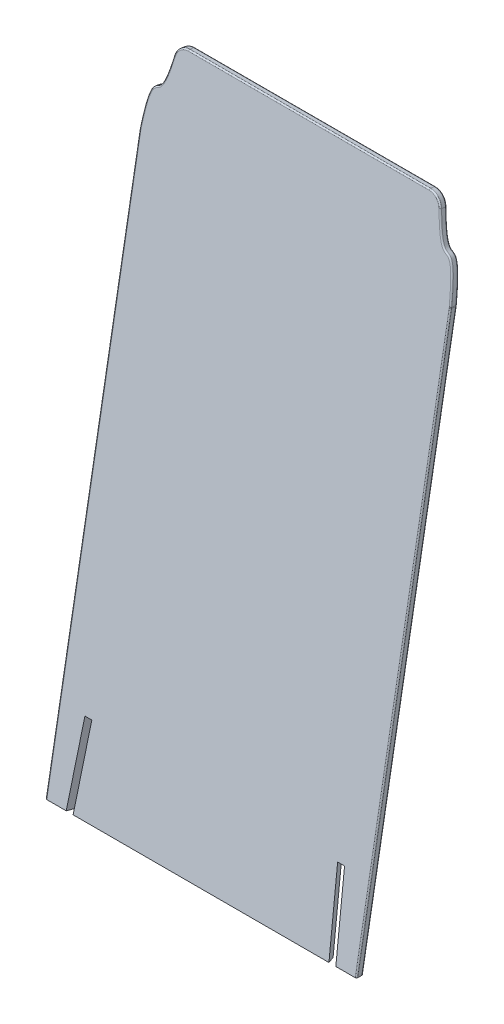
SolidWorks part; units mm, degrees
ref_plane "Front Plane" through (0, 0, 0) normal (0, 0, 1) x (1, 0, 0)
ref_plane "Top Plane" through (0, 0, 0) normal (0, 1, 0) x (1, 0, 0)
ref_plane "Right Plane" through (0, 0, 0) normal (1, 0, 0) x (0, 0, -1)
sketch "Sketch1" plane through (0, 0, 0) normal (1, 0, 0) x (0, 0, -1)
  line L0 (0, 0) -> (211.7119, 1200.6776)
  line L1 (211.7119, 1200.6776) -> (224.2189, 1198.4723)
  line L2 (224.2189, 1198.4723) -> (12.8959, 0)
  line L3 (55, 0) -> (-55, 0) construction
  line L4 (12.8959, 0) -> (0, 0)
  line L5 (0, 55) -> (0, -55) construction
  dimension "D1" = 12.7
  dimension "D2" = 10
  dimension "D3" = 1219.2
extrude "Boss-Extrude1" add sketch "Sketch1" along normal blind 609.6
ref_axis "Axis1" through (0, 1260.7115, 0) along (0, -1, 0)
ref_plane "Plane1" through (0, 0, 0) normal (-0.342, 0, 0.9397) x (0, -1, 0)
sketch "Sketch2" plane through (0, 0, 0) normal (-0.342, 0, 0.9397) x (0, -1, 0)
  line L0 (0, 572.8366) -> (0, 0) construction
  line L1 (0, 38.1) -> (-152.4, 38.1)
  line L2 (0, 38.1) -> (0, 50.8)
  line L3 (0, 50.8) -> (-152.4, 50.8)
  line L4 (-152.4, 38.1) -> (-152.4, 50.8)
  line L5 (-1260.7115, 0) -> (60.0339, 0) construction
  dimension "D1" = 12.7
  dimension "D2" = 152.4
  dimension "D3" = 0
  dimension "D4" = 38.1
ref_plane "Plane2" through (609.6, 0, 0) normal (1, 0, 0) x (0, 0, -1)
ref_axis "Axis2" through (609.6, -60.0339, 0) along (0, 1, 0)
ref_plane "Plane3" through (71.3097, 0, 195.9217) normal (0.342, 0, 0.9397) x (0, 1, 0)
sketch "Sketch3" plane through (71.3097, 0, 195.9217) normal (0.342, 0, 0.9397) x (0, 1, 0)
  line L0 (0, -572.8366) -> (0, 0) construction
  line L1 (0, -534.7366) -> (152.4, -534.7366)
  line L2 (0, -534.7366) -> (0, -522.0366)
  line L3 (0, -522.0366) -> (152.4, -522.0366)
  line L4 (152.4, -534.7366) -> (152.4, -522.0366)
  line L6 (-60.0339, -572.8366) -> (1260.7115, -572.8366) construction
  dimension "D1" = 12.7
  dimension "D2" = 152.4
  dimension "D3" = 0
  dimension "D4" = 38.1
extrude "Cut-Extrude1" cut sketch "Sketch2" against normal blind 609.6 contours L3 L4 L1 L2
extrude "Cut-Extrude2" cut sketch "Sketch3" against normal blind 609.6 contours L3 L4 L1 L2
sketch "Sketch4" plane through (0, 0, 0) normal (0, 0.1736, 0.9848) x (1, 0, 0)
  line L0 (609.6, 1219.2) -> (0, 1219.2) construction
  line L1 (0, 1061.8439) -> (8.115, 1176.4868) construction
  line L2 (8.115, 1176.4868) -> (23.0306, 1126.0577) construction
  line L3 (23.0306, 1126.0577) -> (31.5539, 1123.2166) construction
  line L4 (31.5539, 1123.2166) -> (47.5349, 1219.2) construction
  line L5 (0, -123.3204) -> (0, 123.3204) construction
  line L6 (304.8, 1219.2) -> (304.8, 0) construction
  line L7 (555.5398, 0) -> (54.0602, 0) construction
  line L8 (0, 1061.8439) -> (0, 1219.2)
  line L9 (0, 1241.5585) -> (0, -59.1218) construction
  line L10 (0, 1219.2) -> (47.5349, 1219.2)
  line L11 (609.6, 1061.8439) -> (609.6, 1219.2)
  line L12 (609.6, 1219.2) -> (562.0651, 1219.2)
  line L13 (609.6, 1061.8439) -> (601.485, 1176.4868) construction
  line L14 (601.485, 1176.4868) -> (586.5694, 1126.0577) construction
  line L15 (586.5694, 1126.0577) -> (578.0461, 1123.2166) construction
  line L16 (578.0461, 1123.2166) -> (562.0651, 1219.2) construction
  spline S0 degree 4 poles (0, 1061.8439) (8.115, 1176.4868) (23.0306, 1126.0577) (31.5539, 1123.2166) (47.5349, 1219.2) knots 0 0 0 0 0 1 1 1 1 1
  spline S1 degree 4 poles (609.6, 1061.8439) (601.485, 1176.4868) (586.5694, 1126.0577) (578.0461, 1123.2166) (562.0651, 1219.2) knots 0 0 0 0 0 1 1 1 1 1
extrude "Cut-Extrude3" cut sketch "Sketch4" against normal blind 50.8
fillet "Fillet1" radius 25.4 4 edges at (609.6, 1044.6094, -190.6408) (562.0651, 1199.5749, -217.9654) (0, 1044.6094, -190.6408) (47.5349, 1199.5749, -217.9654)
fillet "Fillet2" radius 2.54 18 edges at (556.9662, 1192.7054, -223.2021) (304.8, 1198.4723, -224.2189) (52.6338, 1192.7054, -223.2021) (0.0163, 1043.5123, -196.8953) (0, 521.3083, -104.8166) (609.6, 521.3083, -104.8166) (609.5837, 1043.5123, -196.8953) (0, 522.411, -92.1151) (0.0163, 1045.7177, -184.3882) (52.6338, 1194.9107, -210.695) (304.8, 1200.6776, -211.7119) (556.9662, 1194.9107, -210.695) (609.5837, 1045.7177, -184.3882) (609.6, 522.411, -92.1151)
